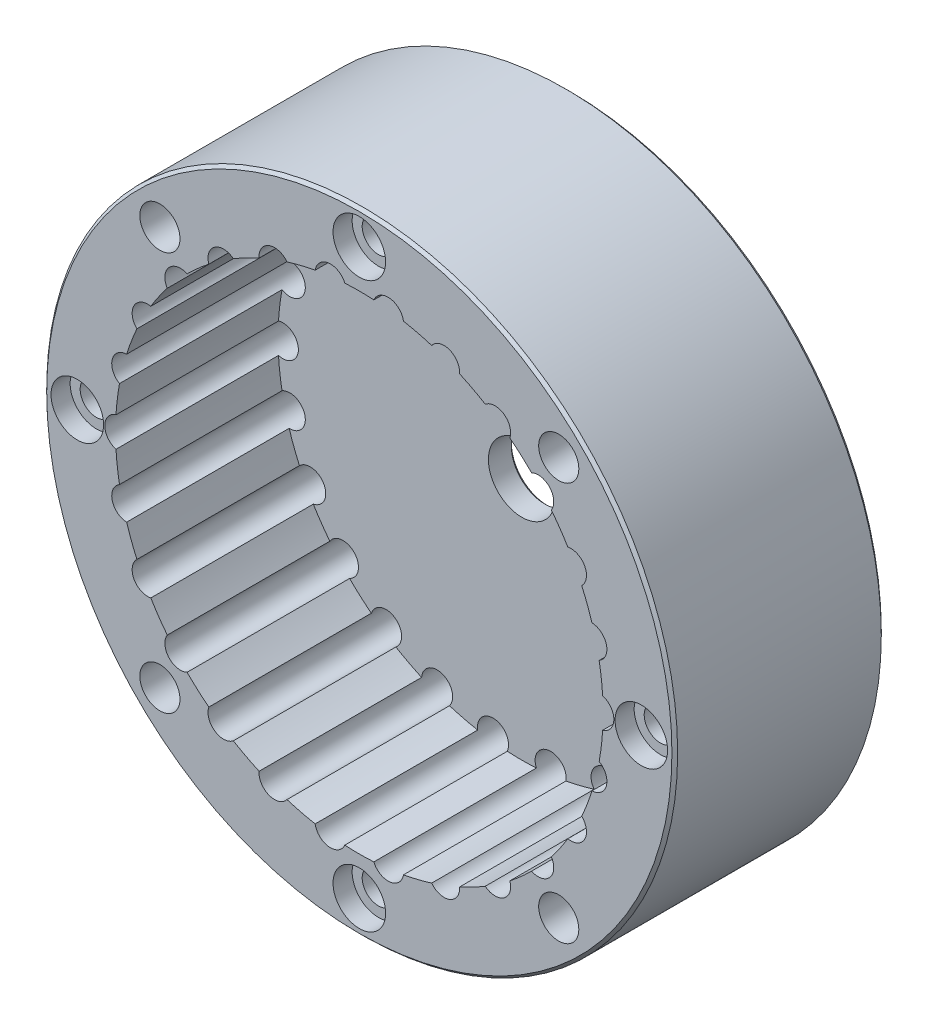
SolidWorks part; units mm, degrees
ref_plane "Front Plane" through (0, 0, 0) normal (0, 0, 1) x (1, 0, 0)
ref_plane "Top Plane" through (0, 0, 0) normal (0, 1, 0) x (1, 0, 0)
ref_plane "Right Plane" through (0, 0, 0) normal (1, 0, 0) x (0, 0, -1)
sketch "Sketch1" plane through (0, 0, 0) normal (0, 0, 1) x (1, 0, 0)
  line L0 (-25, 0) -> (25, 0) construction
  circle A0 centre (0, 0) radius 33
  circle A1 centre (0, 0) radius 25.5
  circle A2 centre (25, 0) radius 1.625
  circle A3 centre (24.2735, -5.9829) radius 1.625
  circle A4 centre (22.1364, -11.6181) radius 1.625
  circle A5 centre (18.7128, -16.5781) radius 1.625
  circle A6 centre (14.2016, -20.5746) radius 1.625
  circle A7 centre (8.8651, -23.3754) radius 1.625
  circle A8 centre (3.0134, -24.8177) radius 1.625
  circle A9 centre (-3.0134, -24.8177) radius 1.625
  circle A10 centre (-8.8651, -23.3754) radius 1.625
  circle A11 centre (-14.2016, -20.5746) radius 1.625
  circle A12 centre (-18.7128, -16.5781) radius 1.625
  circle A13 centre (-22.1364, -11.6181) radius 1.625
  circle A14 centre (-24.2735, -5.9829) radius 1.625
  circle A15 centre (-25, 0) radius 1.625
  circle A16 centre (-24.2735, 5.9829) radius 1.625
  circle A17 centre (-22.1364, 11.6181) radius 1.625
  circle A18 centre (-18.7128, 16.5781) radius 1.625
  circle A19 centre (-14.2016, 20.5746) radius 1.625
  circle A20 centre (-8.8651, 23.3754) radius 1.625
  circle A21 centre (-3.0134, 24.8177) radius 1.625
  circle A22 centre (3.0134, 24.8177) radius 1.625
  circle A23 centre (8.8651, 23.3754) radius 1.625
  circle A24 centre (14.2016, 20.5746) radius 1.625
  circle A25 centre (18.7128, 16.5781) radius 1.625
  circle A26 centre (22.1364, 11.6181) radius 1.625
  circle A27 centre (24.2735, 5.9829) radius 1.625
  point P7 (0, 0)
  point P61 (0, 0)
  dimension "D1" = 66
  dimension "D2" = 51
  dimension "D4" = 3.25
  dimension "D3" = 50
  dimension "D5" = 26
extrude "Boss-Extrude2" add sketch "Sketch1" along normal blind 17 contours A0 A27 A1 A2 A3 A4 A5 A6 A7 A8 A9 A10 A11 A12 A13 A14 A15 A16 A17 A18 A19 A20 A21 A22 A23 A24 A25 | A1 A17 | A1 A18 | A1 A19 | A1 A20 | A1 A21 | A1 A22 | A1 A23 | A1 A24 | A1 A25 | A1 A26 | A1 A27 | A1 A2 | A1 A4 | A1 A5 | A1 A6 | A1 A7 | A1 A8 | A1 A9 | A1 A10 | A1 A11 | A1 A12 | A1 A13 | A1 A14 | A1 A15 | A1 A16 | A1 A3 region at (-32.0666, 0, 0) region at (25.9577, 0, 0) region at (25.2034, 6.2121, 0) region at (25.2034, -6.2121, 0) region at (22.9844, 12.0631, 0) region at (22.9844, -12.0631, 0) region at (19.4296, 17.2131, 0) region at (19.4296, -17.2131, 0) region at (14.7456, 21.3628, 0) region at (14.7456, -21.3628, 0) region at (9.2047, 24.2709, 0) region at (9.2047, -24.2709, 0) region at (3.1289, 25.7684, 0) region at (3.1289, -25.7684, 0) region at (-3.1289, 25.7684, 0) region at (-3.1289, -25.7684, 0) region at (-9.2047, 24.2709, 0) region at (-9.2047, -24.2709, 0) region at (-14.7456, 21.3628, 0) region at (-14.7456, -21.3628, 0) region at (-19.4296, 17.2131, 0) region at (-19.4296, -17.2131, 0) region at (-22.9844, 12.0631, 0) region at (-22.9844, -12.0631, 0) region at (-25.2034, 6.2121, 0) region at (-25.2034, -6.2121, 0) region at (-25.9577, 0, 0)
extrude "Boss-Extrude3" add sketch "Sketch1<3>" against normal blind 5 contours A15 L0 A2 A1 A27 A26 A25 A24 A23 A22 A21 A20 A19 A18 A17 A16 | L0 A15 A1 A14 A13 A12 A11 A10 A9 A8 A7 A6 A5 A4 A3 A2 | A0 A27 A1 A2 A3 A4 A5 A6 A7 A8 A9 A10 A11 A12 A13 A14 A15 A16 A17 A18 A19 A20 A21 A22 A23 A24 A25 | A9 | A10 | A11 | A12 | A13 | A14 | A15 | A16 | A17 | A18 | A19 | A20 | A21 | A22 | A23 | A24 | A25 | A26 | A27 | A2 | A3 | A4 | A5 | A6 | A7 | A8 region at (0, 10.4477, 0) region at (0, -10.4477, 0) region at (-32.0666, 0, 0)
sketch "Sketch1<3>" plane through (0, 0, 0) normal (0, 0, 1) x (1, 0, 0) same geometry as "Sketch1"
extrude "Cut-Extrude4" cut sketch "Sketch1<5>" against normal blind 3 and the other way through all contours A18 | A19 | A20 | A21 | A22 | A23 | A24 | A25 | A26 | A27 | A2 | A3 | A4 | A5 | A6 | A7 | A8 | A9 | A10 | A11 | A12 | A13 | A14 | A15 | A16 | A17
sketch "Sketch1<5>" plane through (0, 0, 0) normal (0, 0, 1) x (1, 0, 0) same geometry as "Sketch1"
sketch "Sketch3" plane through (0, 0, 0) normal (0, 0, 1) x (1, 0, 0)
  line L0 (0, 29.5) -> (0, 0) construction
  circle A0 centre (0, 29.5) radius 1.7
  circle A1 centre (29.5, 0) radius 1.7
  circle A2 centre (0, -29.5) radius 1.7
  circle A3 centre (-29.5, 0) radius 1.7
  circle A8 centre (0, 0) radius 3.5
  point P0 (0, 0)
  point P21 (0, 0)
  dimension "D3" = 4
  dimension "D4" = 7
  dimension "D1" = 29.5
  dimension "D2" = 3.4
extrude "Cut-Extrude6" cut sketch "Sketch3" against normal through all both and the other way through all
sketch "Sketch4" plane through (0, 0, -5) normal (0, 0, -1) x (-1, 0, 0)
  circle A0 centre (0, 0) radius 10
  dimension "D1" = 20
extrude "Cut-Extrude7" cut sketch "Sketch4" against normal blind 2.3
sketch "Sketch5" plane through (0, 0, 17) normal (0, 0, 1) x (1, 0, 0)
  line L0 (0, 29.5) -> (0, -29.5) construction
sketch "Sketch6" plane through (0, 0, 17) normal (0, 0, 1) x (1, 0, 0)
  line L1 (-20.8597, 20.8597) -> (0, 0) construction
  line L2 (0, 29.5) -> (0, -29.5) construction
  circle A0 centre (-20.8597, 20.8597) radius 2.1
  circle A1 centre (20.8597, 20.8597) radius 2.1
  circle A2 centre (20.8597, -20.8597) radius 2.1
  circle A3 centre (-20.8597, -20.8597) radius 2.1
  point P15 (0, 0)
  dimension "D1" = 4.2
  dimension "D2" = 29.5
  dimension "D3" = 45
  dimension "D4" = 4
extrude "Cut-Extrude8" cut sketch "Sketch6" against normal blind 10
sketch "Sketch7" plane through (0, 0, 17) normal (0, 0, 1) x (1, 0, 0)
  circle A0 centre (0, 29.5) radius 2.75
  circle A1 centre (29.5, 0) radius 2.75
  circle A2 centre (0, -29.5) radius 2.75
  circle A3 centre (-29.5, 0) radius 2.75
  point P12 (0, 0)
  dimension "D1" = 5.5
  dimension "D2" = 4
extrude "Cut-Extrude9" cut sketch "Sketch7" against normal blind 2
chamfer "Chamfer1" distance 0.4 angle 45 5 edges at (-10, 0, -5) (1.7, -29.5, -5) (-27.8, 0, -5) (31.2, 0, -5) (1.7, 29.5, -5)
chamfer "Chamfer2" distance 0.3 angle 45 1 edges at (-3.5, 0, -2.7)
chamfer "Chamfer3" distance 0.4 angle 45 1 edges at (33, 0, -5)
chamfer "Chamfer4" distance 0.3 angle 45 1 edges at (33, 0, 17)
equation "\"N_pins\"= 26"
equation "\"N_lobes\"= \"N_pins\" - 1"
equation "\"R_pc\"= 25"
equation "\"D_pin\"= 3.25mm"
equation "\"R_pin\"= \"D_pin\" / 2"
equation "\"ecc\"= 0.72"
equation "\"t_disc\"= 7"
equation "\"N_out\"= 8"
equation "\"D_outc\"=22"
equation "\"D_roller\"= 5"
equation "\"D_outhole\"= \"D_roller\" + 2 * \"ecc\""
equation "\"D_cam_OD\"= 21"
equation "\"D_cam_ID\"= 10"
equation "\"clr_bore\"= 1"
equation "\"D_bore\"= 2 * \"R_pc\" + \"clr_bore\""
equation "\"t_wall\"= 7.5"
equation "\"D_housing\"= \"D_bore\" + 2 * \"t_wall\""
equation "\"D1@Sketch1\"=\"D_housing\""
equation "\"D2@Sketch1\"=\"D_bore\""
equation "\"D3@Sketch1\"=2 * \"R_pc\""
equation "\"D4@Sketch1\"=\"D_pin\""
equation "\"L_housing\"=17"
equation "\"D1@Boss-Extrude2\"=\"L_housing\""
